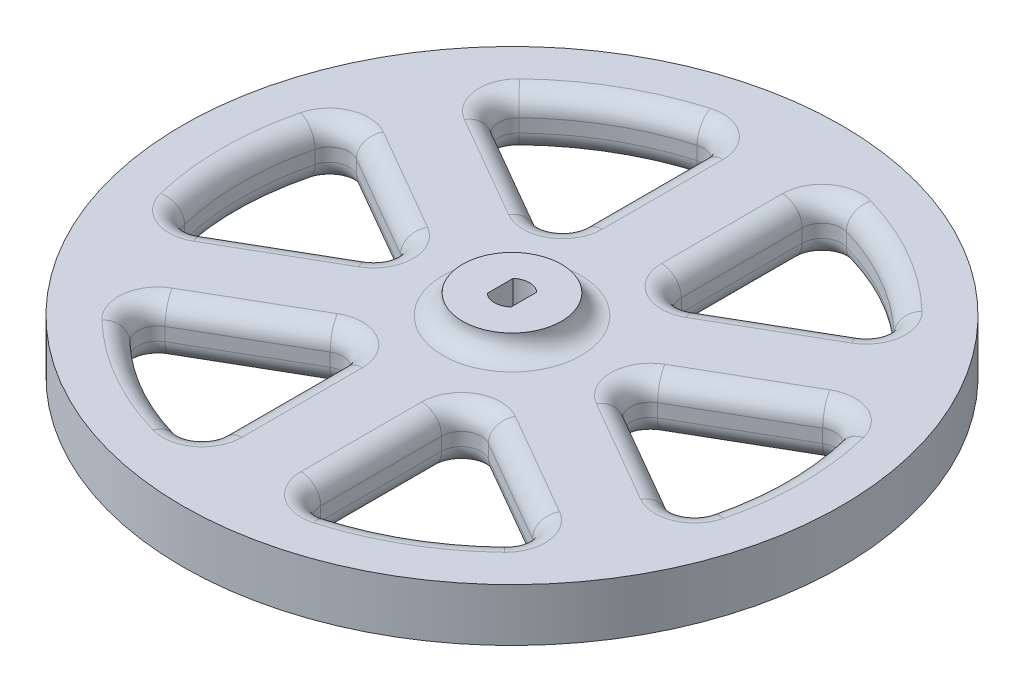
SolidWorks part; units mm, degrees
ref_plane "Front Plane" through (0, 0, 0) normal (0, 0, 1) x (1, 0, 0)
ref_plane "Top Plane" through (0, 0, 0) normal (0, 1, 0) x (1, 0, 0)
ref_plane "Right Plane" through (0, 0, 0) normal (1, 0, 0) x (0, 0, -1)
sketch "Sketch1" plane through (0, 0, 0) normal (0, 1, 0) x (1, 0, 0)
  circle A0 centre (0, 0) radius 50
  dimension "D1" = 100
extrude "Boss-Extrude1" add sketch "Sketch1" along normal blind 8
sketch "Sketch2" plane through (0, 8, 0) normal (0, 1, 0) x (1, 0, 0)
  line L0 (-1.8, 1.9449) -> (-1.8, -1.9449)
  line L1 (1.8, 1.9449) -> (1.8, -1.9449)
  arc A0 (-1.8, -1.9449) -> (1.8, -1.9449) centre (0, 0) ccw
  arc A1 (1.8, 1.9449) -> (-1.8, 1.9449) centre (0, 0) ccw
  circle A2 centre (0, 0) radius 7.5
  dimension "D1" = 5.3
  dimension "D4" = 15
  dimension "D2" = 1.8
  dimension "D3" = 3.6
extrude "Boss-Extrude4" add sketch "Sketch2" along normal blind 3
ref_plane "Plane1" through (-1.8, 8, -1.9449) normal (0, 0, 1) x (1, 0, 0)
sketch "Sketch5" plane through (0, 8, 0) normal (0, 1, 0) x (1, 0, 0)
  line L0 (-1.8, 1.9449) -> (-1.8, -1.9449)
  line L1 (1.8, 1.9449) -> (1.8, -1.9449)
  arc A0 (-1.8, -1.9449) -> (1.8, -1.9449) centre (0, 0) ccw
  arc A1 (1.8, 1.9449) -> (-1.8, 1.9449) centre (0, 0) ccw
  dimension "D1" = 5.3
  dimension "D2" = 1.8
  dimension "D3" = 3.6
extrude "Cut-Extrude4" cut sketch "Sketch5" against normal through all
sketch "Sketch7" plane through (0, 8, 0) normal (0, 1, 0) x (1, 0, 0)
  line L0 (-7.5, 40.3082) -> (-7.5, 12.9904)
  line L1 (7.5, -40.3082) -> (7.5, -12.9904)
  line L2 (-1.8, 1.9449) -> (-1.8, -1.9449) construction
  line L3 (1.8, -1.9449) -> (1.8, 1.9449) construction
  line L4 (-31.1579, 26.6493) -> (-7.5, 12.9904)
  line L5 (-38.6579, 13.6589) -> (-15, 0)
  line L6 (-38.6579, -13.6589) -> (-15, 0)
  line L7 (-31.1579, -26.6493) -> (-7.5, -12.9904)
  line L10 (7.5, 12.9904) -> (31.1579, 26.6493)
  line L11 (7.5, 12.9904) -> (7.5, 40.3082)
  line L12 (15, 0) -> (38.6579, -13.6589)
  line L13 (15, 0) -> (38.6579, 13.6589)
  line L15 (7.5, -12.9904) -> (31.1579, -26.6493)
  line L17 (-7.5, -12.9904) -> (-7.5, -40.3082)
  arc A0 (7.5, -40.3082) -> (31.1579, -26.6493) centre (0, 0) ccw
  circle A1 centre (0, 0) radius 7.5 construction
  arc A2 (-38.6579, 13.6589) -> (-38.6579, -13.6589) centre (0, 0) ccw
  arc A3 (-7.5, 40.3082) -> (-31.1579, 26.6493) centre (0, 0) ccw
  arc A4 (31.1579, 26.6493) -> (7.5, 40.3082) centre (0, 0) ccw
  arc A5 (-31.1579, -26.6493) -> (-7.5, -40.3082) centre (0, 0) ccw
  arc A6 (38.6579, -13.6589) -> (38.6579, 13.6589) centre (0, 0) ccw
  dimension "D4" = 82
  dimension "D1" = 60
  dimension "D2" = 60
  dimension "D3" = 60
extrude "Cut-Extrude6" cut sketch "Sketch7" against normal through all
fillet "Fillet4" radius 3 1 edges at (0, 8, 7.5)
fillet "Fillet5" radius 3 12 edges at (-31.1579, 4, -26.6493) (-31.1579, 4, 26.6493) (-38.6579, 4, -13.6589) (-7.5, 4, -40.3082) (7.5, 4, -40.3082) (38.6579, 4, -13.6589) (31.1579, 4, 26.6493) (-7.5, 4, 40.3082) (-38.6579, 4, 13.6589) (7.5, 4, 40.3082) (38.6579, 4, 13.6589) (31.1579, 4, -26.6493)
fillet "Fillet6" radius 3 6 edges at (-15, 4, 0) (-7.5, 4, 12.9904) (7.5, 4, 12.9904) (15, 4, 0) (7.5, 4, -12.9904) (-7.5, 4, -12.9904)
fillet "Fillet7" radius 3 36 edges at (29.3555, 8, -26.989) (19.9389, 8, -20.172) (9, 8, -15.5885) (7.5, 8, -27.3535) (8.6954, 8, -38.9171) (-8.6954, 8, -38.9171) (-7.5, 8, -27.3535) (-9, 8, -15.5885) (-19.9389, 8, -20.172) (-29.3555, 8, -26.989) (-38.0509, 8, -11.9281) (-27.4389, 8, -7.1816) (-18, 8, 0) (-27.4389, 8, 7.1816) (-38.0509, 8, 11.9281) (-29.3555, 8, 26.989) (-19.9389, 8, 20.172) (-9, 8, 15.5885) (-7.5, 8, 27.3535) (-8.6954, 8, 38.9171) (9, 8, 15.5885) (19.9389, 8, 20.172) (29.3555, 8, 26.989) (20.5, 8, 35.507) (8.6954, 8, 38.9171) (18, 8, 0) (27.4389, 8, -7.1816) (38.0509, 8, -11.9281) (41, 8, 0) (38.0509, 8, 11.9281) (20.5, 8, -35.507) (-20.5, 8, -35.507) (-41, 8, 0) (-20.5, 8, 35.507) (7.5, 8, 27.3535) (27.4389, 8, 7.1816)
fillet "Fillet8" radius 3 36 edges at (38.0509, 0, -11.9281) (41, 0, 0) (38.0509, 0, 11.9281) (27.4389, 0, 7.1816) (18, 0, 0) (9, 0, 15.5885) (19.9389, 0, 20.172) (29.3555, 0, 26.989) (20.5, 0, 35.507) (8.6954, 0, 38.9171) (-9, 0, 15.5885) (-7.5, 0, 27.3535) (-8.6954, 0, 38.9171) (-20.5, 0, 35.507) (-29.3555, 0, 26.989) (-18, 0, 0) (-27.4389, 0, 7.1816) (-38.0509, 0, 11.9281) (-41, 0, 0) (-38.0509, 0, -11.9281) (-29.3555, 0, -26.989) (-20.5, 0, -35.507) (-8.6954, 0, -38.9171) (-7.5, 0, -27.3535) (-9, 0, -15.5885) (8.6954, 0, -38.9171) (20.5, 0, -35.507) (29.3555, 0, -26.989) (19.9389, 0, -20.172) (9, 0, -15.5885) (27.4389, 0, -7.1816) (7.5, 0, 27.3535) (-19.9389, 0, 20.172) (-27.4389, 0, -7.1816) (-19.9389, 0, -20.172) (7.5, 0, -27.3535)
sketch "Sketch9" plane through (-1.8, 8, -1.9449) normal (0, 0, 1) x (1, 0, 0)
ref_plane "Plane2" through (0, 0, 0) normal (0, 0, -1) x (-1, 0, 0)
